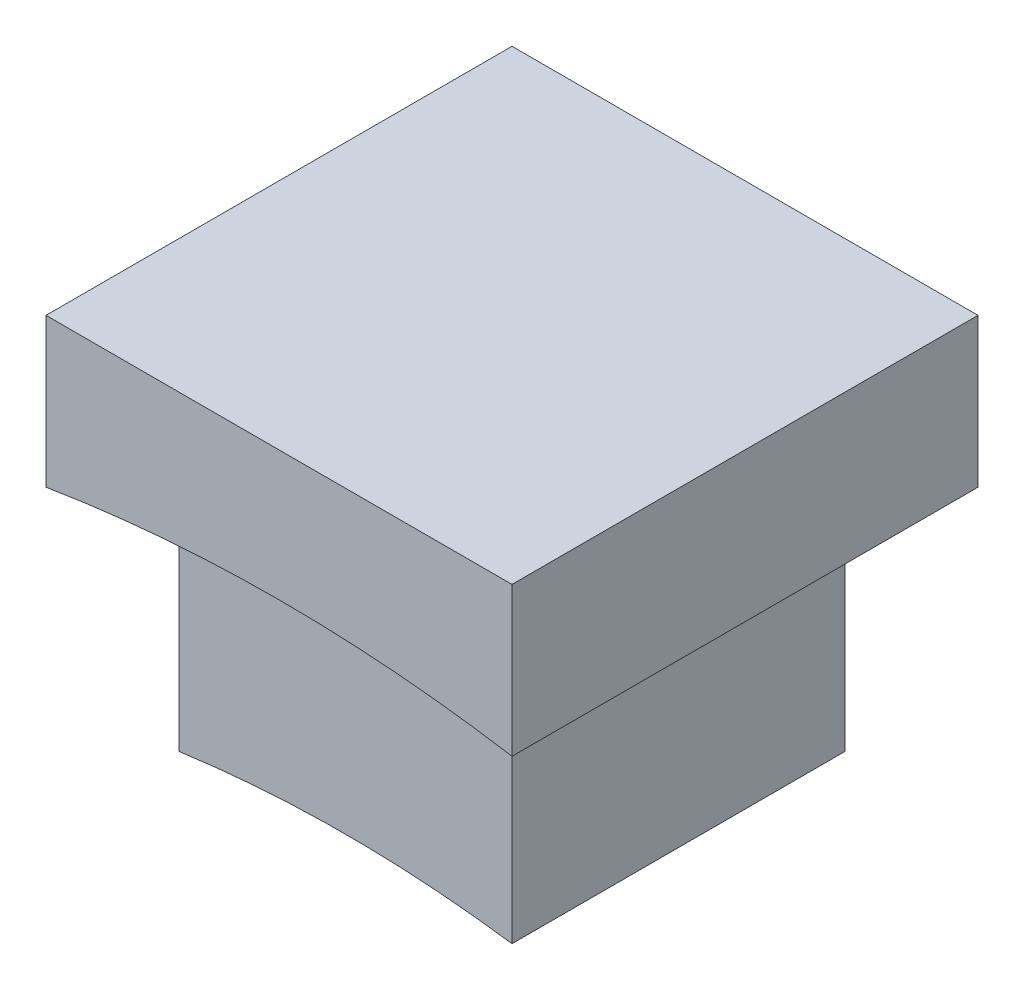
SolidWorks part; units mm, degrees
ref_plane "Front Plane" through (0, 0, 0) normal (0, 0, 1) x (1, 0, 0)
ref_plane "Top Plane" through (0, 0, 0) normal (0, 1, 0) x (1, 0, 0)
ref_plane "Right Plane" through (0, 0, 0) normal (1, 0, 0) x (0, 0, -1)
sketch "Sketch1" plane through (0, 0, 0) normal (0, 1, 0) x (1, 0, 0)
  line L1 (-7, -7) -> (7, -7)
  line L2 (-7, -7) -> (-7, 7)
  line L3 (-7, 7) -> (7, 7)
  line L4 (7, -7) -> (7, 7)
  line L5 (-7, -7) -> (7, 7) construction
  line L6 (-7, 7) -> (7, -7) construction
  point P0 (3.5667, -0.3637)
  point P3 (0, 0)
  point P8 (0, 0)
  dimension "D2" = 14
  dimension "D3" = 14
extrude "Boss-Extrude1" add sketch "Sketch1" along normal blind 10
sketch "Sketch2" plane through (0, 0, 0) normal (0, 0, 1) x (1, 0, 0)
  circle A0 centre (0, -37) radius 43.1
  point P2 (0, 0)
  point P4 (0, -37.779)
  point P5 (0, 0)
  point P6 (0, -36.6575)
  dimension "D1" = 86.2
  dimension "D2" = 37
extrude "Cut-Extrude1" cut sketch "Sketch2" against normal through all both and the other way through all
sketch "Sketch3" plane through (0, 10, 0) normal (0, 1, 0) x (1, 0, 0)
  line L1 (-5, -5) -> (5, -5)
  line L2 (-5, -5) -> (-5, 5)
  line L3 (-5, 5) -> (5, 5)
  line L4 (5, -5) -> (5, 5)
  line L5 (-5, -5) -> (5, 5) construction
  line L6 (-5, 5) -> (5, -5) construction
  point P0 (0, 0)
  dimension "D2" = 10
  dimension "D3" = 10
extrude "Boss-Extrude2" add sketch "Sketch3" against normal blind 15
sketch "Sketch5" plane through (0, 0, 0) normal (0, 0, 1) x (1, 0, 0)
  circle A0 centre (0, -37) radius 36
  point P2 (0, 0)
  point P4 (0, -33.1367)
  dimension "D1" = 72
  dimension "D2" = 37
extrude "Cut-Extrude2" cut sketch "Sketch5" against normal through all both and the other way through all
